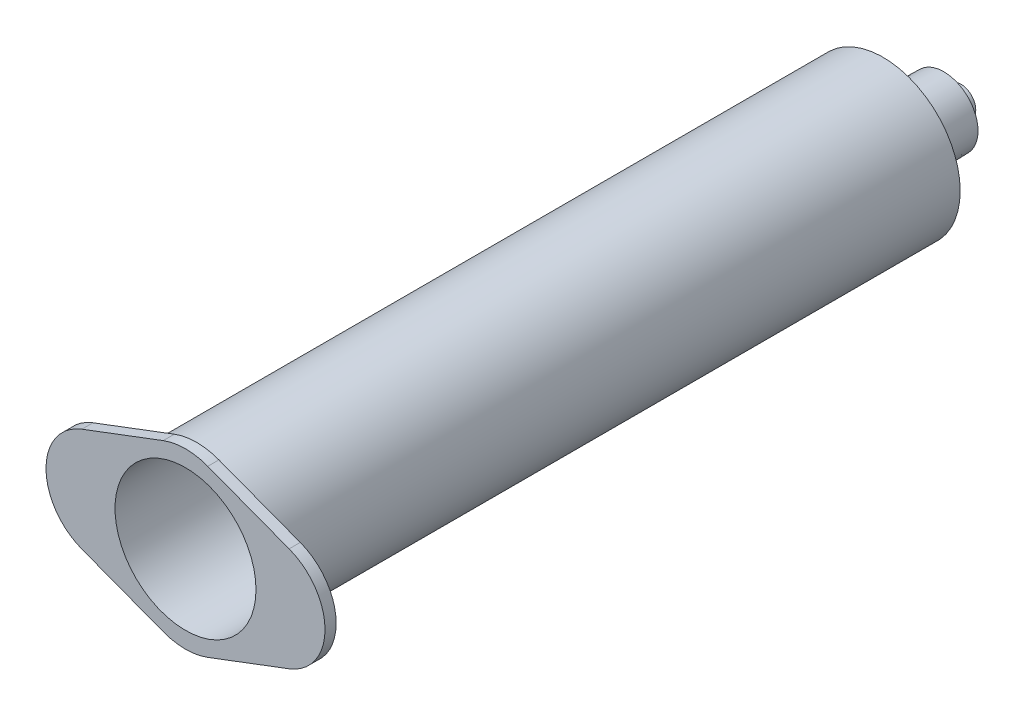
SolidWorks part; units mm, degrees
ref_plane "Front Plane" through (0, 0, 0) normal (0, 0, 1) x (1, 0, 0)
ref_plane "Top Plane" through (0, 0, 0) normal (0, 1, 0) x (1, 0, 0)
ref_plane "Right Plane" through (0, 0, 0) normal (1, 0, 0) x (0, 0, -1)
sketch "Sketch1" plane through (0, 0, 0) normal (0, 0, 1) x (1, 0, 0)
  circle A0 centre (0, 0) radius 9.5
  circle A1 centre (0, 0) radius 10.4
  dimension "D1" = 20.8
  dimension "D2" = 19
extrude "Boss-Extrude1" add sketch "Sketch1" along normal blind 92.5
sketch "Sketch2" plane through (0, 0, 0) normal (1, 0, 0) x (0, 0, -1)
  line L0 (0, 0) -> (12.896, 0) construction
  line L1 (0, 10.4) -> (1.2, 4.8)
  line L2 (1.2, 4.8) -> (8.2, 4.6)
  line L3 (8.2, 4.6) -> (8.2, 3.8)
  line L4 (8.2, 3.8) -> (2.2, 3.8)
  line L5 (2.2, 3.8) -> (2.2, 2)
  line L6 (2.2, 2) -> (10.5, 2)
  line L7 (10.5, 2) -> (10.5, 0.97)
  line L8 (10.5, 0.97) -> (1.2, 0.97)
  line L9 (1.2, 0.97) -> (1.2, 3.9)
  line L10 (1.2, 3.9) -> (0, 9.5)
  line L11 (0, 9.5) -> (0, 10.4)
  point P16 (10.0952, 3.321)
  point P17 (0, 0)
  point P18 (1.2, 1.2603)
  dimension "D1" = 1.94
  dimension "D2" = 4
  dimension "D3" = 9.2
  dimension "D4" = 9.6
  dimension "D5" = 7
  dimension "D6" = 2.3
  dimension "D7" = 1.2
  dimension "D8" = 6
  dimension "D9" = 0.8
revolve "Revolve1" add sketch "Sketch2" angle 360 about L0
sketch "Sketch3" plane through (0, 0, 92.5) normal (0, 0, 1) x (1, 0, 0)
  line L0 (0, 11.7) -> (0, 0) construction
  line L1 (0, 0) -> (-18.8, 0) construction
  line L2 (-3, 11.1511) -> (-13.9652, 7)
  line L3 (-3, -11.1511) -> (-13.9652, -7)
  line L4 (3, -11.1511) -> (13.9652, -7)
  line L5 (3, 11.1511) -> (13.9652, 7)
  circle A0 centre (0, 0) radius 9.5 construction
  circle A1 centre (0, 0) radius 9.5
  arc A2 (-13.9652, -7) -> (-13.9652, 7) centre (-11.3152, 0) cw
  arc A3 (3, 11.1511) -> (-3, 11.1511) centre (0, 3.2267) ccw
  arc A4 (3, -11.1511) -> (-3, -11.1511) centre (0, -3.2267) cw
  arc A5 (13.9652, -7) -> (13.9652, 7) centre (11.3152, 0) ccw
  point P9 (-9.5, 0)
  point P10 (0, 10.8094)
  point P11 (0, 9.5)
  point P12 (-15.5116, 0)
  point P13 (-8.8449, 9.6795)
  point P18 (-18.8, 0)
  point P19 (0, 0)
  point P24 (0, 11.7)
  dimension "D5" = 19
  dimension "D1" = 2.2
  dimension "D2" = 9.3
  dimension "D3" = 14
  dimension "D4" = 6
extrude "Boss-Extrude2" add sketch "Sketch3" along normal blind 1.5
